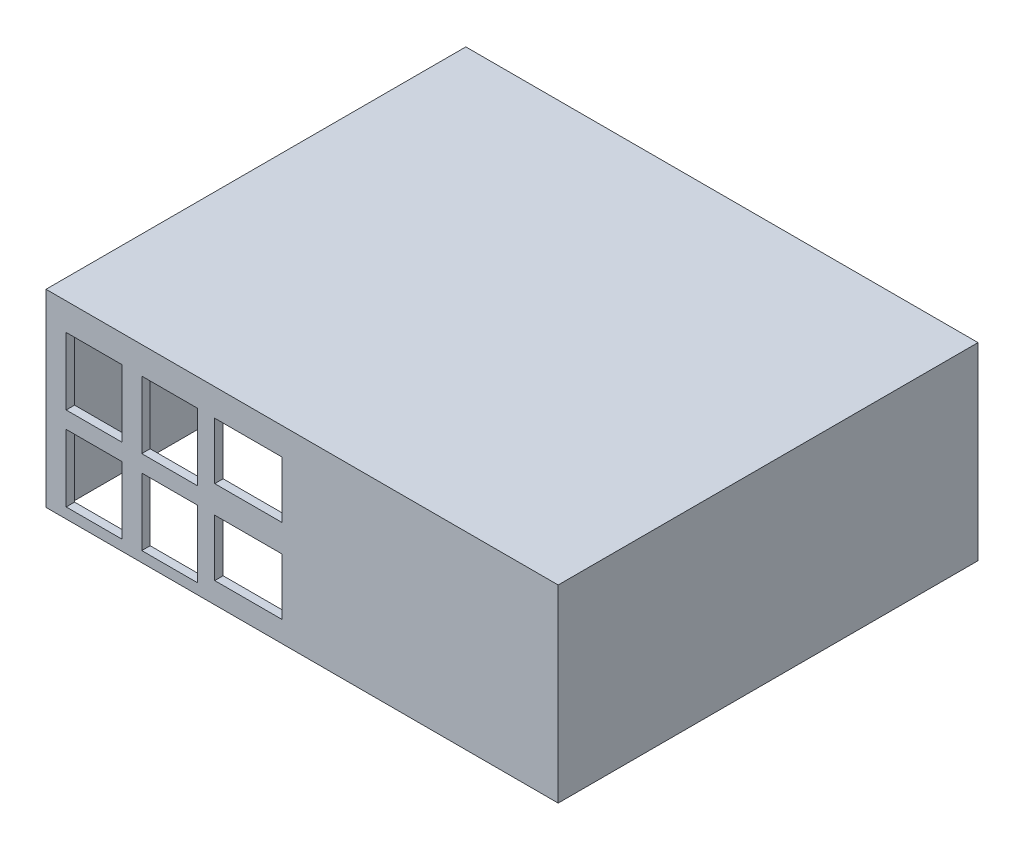
SolidWorks part; units mm, degrees
ref_plane "Front Plane" through (0, 0, 0) normal (0, 0, 1) x (1, 0, 0)
ref_plane "Top Plane" through (0, 0, 0) normal (0, 1, 0) x (1, 0, 0)
ref_plane "Right Plane" through (0, 0, 0) normal (1, 0, 0) x (0, 0, -1)
sketch "Sketch1" plane through (0, 0, 0) normal (0, 1, 0) x (1, 0, 0)
  line L1 (-61, -50) -> (61, -50)
  line L2 (-61, -50) -> (-61, 50)
  line L3 (-61, 50) -> (61, 50)
  line L4 (61, -50) -> (61, 50)
  line L5 (-61, -50) -> (61, 50) construction
  line L6 (-61, 50) -> (61, -50) construction
  point P0 (0, 0)
  dimension "D1" = 100
  dimension "D2" = 122
extrude "Boss-Extrude1" add sketch "Sketch1" along normal blind 45
shell "Shell1" thickness 2 removed face at (0, 0, 0)
sketch "Sketch3" plane through (0, 43, 0) normal (0, -1, 0) x (1, 0, 0)
  line L0 (-55, 24.5) -> (-6, 24.5) construction
  line L1 (-6, 24.5) -> (-6, -33.5) construction
  line L2 (-6, -33.5) -> (-55, -33.5) construction
  line L3 (-55, -33.5) -> (-55, 24.5) construction
  line L5 (-59, 48) -> (59, 48) construction
  line L6 (-55, -4.5) -> (-59, -4.5) construction
  line L7 (-59, -48) -> (-59, 48) construction
  line L8 (-6, -4.5) -> (59, -4.5) construction
  line L9 (59, 48) -> (59, -48) construction
  circle A0 centre (-55, 24.5) radius 2.5
  circle A1 centre (-6, 24.5) radius 2.5
  circle A2 centre (-55, -33.5) radius 2.5
  circle A3 centre (-6, -33.5) radius 2.5
  dimension "D4" = 5
  dimension "D1" = 58
  dimension "D2" = 49
  dimension "D3" = 23.5
  dimension "D5" = 4
extrude "Boss-Extrude2" add sketch "Sketch3" along normal blind 3
sketch "Sketch4" plane through (0, 40, 0) normal (0, -1, 0) x (1, 0, 0)
  circle A0 centre (-6, 24.5) radius 1.025
  circle A1 centre (-55, 24.5) radius 1.025
  circle A2 centre (-55, -33.5) radius 1.025
  circle A3 centre (-6, -33.5) radius 1.025
  point P12 (0, 0)
  point P13 (0, 0)
  dimension "D1" = 2.05
extrude "Cut-Extrude1" cut sketch "Sketch4" against normal blind 2.7
sketch "Sketch17" plane through (0, 0, 50) normal (0, 0, 1) x (1, 0, 0)
  line L0 (0, 45) -> (0, 0) construction
  line L1 (-61, 45) -> (61, 45) construction
  line L2 (61, 38.5) -> (-61, 38.5) construction
  line L3 (-42.94, 22.5) -> (-56.19, 22.5)
  line L4 (-42.94, 22.5) -> (-42.94, 38.5)
  line L5 (-42.94, 38.5) -> (-56.19, 38.5)
  line L6 (-56.19, 22.5) -> (-56.19, 38.5)
  line L7 (-42.94, 22.5) -> (-56.19, 38.5) construction
  line L8 (-42.94, 38.5) -> (-56.19, 22.5) construction
  line L9 (-24.94, 22.5) -> (-38.19, 22.5)
  line L10 (-24.94, 22.5) -> (-24.94, 38.5)
  line L11 (-24.94, 38.5) -> (-38.19, 38.5)
  line L12 (-38.19, 22.5) -> (-38.19, 38.5)
  line L13 (-24.94, 22.5) -> (-38.19, 38.5) construction
  line L14 (-24.94, 38.5) -> (-38.19, 22.5) construction
  line L15 (-4.81, 25) -> (-20.81, 25)
  line L16 (-4.81, 25) -> (-4.81, 38.5)
  line L17 (-4.81, 38.5) -> (-20.81, 38.5)
  line L18 (-20.81, 25) -> (-20.81, 38.5)
  line L19 (-4.81, 25) -> (-20.81, 38.5) construction
  line L20 (-4.81, 38.5) -> (-20.81, 25) construction
  line L21 (61, 45) -> (61, 0) construction
  line L22 (-61, 45) -> (-61, 0) construction
  line L23 (-4.81, 31.75) -> (61, 31.75) construction
  line L24 (-56.19, 30.5) -> (-61, 30.5) construction
  point P5 (-49.565, 30.5)
  point P10 (-31.565, 30.5)
  point P15 (-12.81, 31.75)
  dimension "D1" = 6.5
  dimension "D2" = 13.5
  dimension "D3" = 16
  dimension "D4" = 16
  dimension "D5" = 13.25
  dimension "D6" = 4.75
  dimension "D7" = 4.13
  dimension "D8" = 4.81
extrude "Cut-Extrude2" cut sketch "Sketch17" against normal up to surface (2 mm away) up to face at (0, 21.5, 48)
pattern_linear "LPattern1" count 2 spacing 20 along (0, -1, 0) of "Cut-Extrude2"
